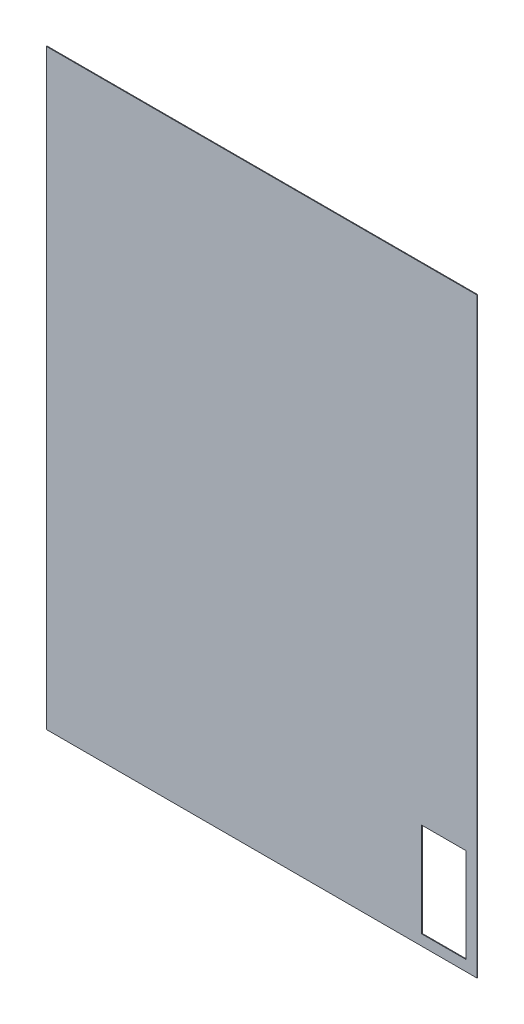
SolidWorks part; units mm, degrees
ref_plane "Front Plane" through (0, 0, 0) normal (0, 0, 1) x (1, 0, 0)
ref_plane "Top Plane" through (0, 0, 0) normal (0, 1, 0) x (1, 0, 0)
ref_plane "Right Plane" through (0, 0, 0) normal (1, 0, 0) x (0, 0, -1)
sketch "Sketch1" plane through (0, 0, 0) normal (0, 0, 1) x (1, 0, 0)
  line L1 (0, 0) -> (1215, 0)
  line L2 (0, 0) -> (0, 1670)
  line L3 (0, 1670) -> (1215, 1670)
  line L4 (1215, 0) -> (1215, 1670)
  line L5 (1185, 30) -> (1059, 30)
  line L6 (1185, 30) -> (1185, 296)
  line L7 (1185, 296) -> (1059, 296)
  line L8 (1059, 30) -> (1059, 296)
  dimension "D1" = 1215
  dimension "D2" = 1670
  dimension "D3" = 126
  dimension "D4" = 30
  dimension "D5" = 30
  dimension "D6" = 266
extrude "Boss-Extrude1" add sketch "Sketch1" along normal blind 2
